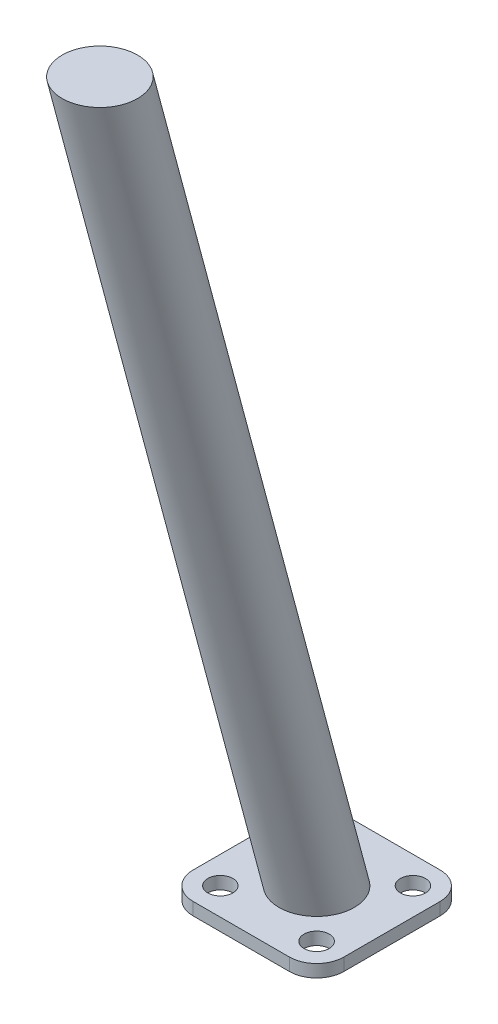
SolidWorks part; units mm, degrees
ref_plane "Front Plane" through (0, 0, 0) normal (0, 0, 1) x (1, 0, 0)
ref_plane "Top Plane" through (0, 0, 0) normal (0, 1, 0) x (1, 0, 0)
ref_plane "Right Plane" through (0, 0, 0) normal (1, 0, 0) x (0, 0, -1)
sketch "Sketch1" plane through (0, 0, 0) normal (0, 1, 0) x (1, 0, 0)
  line L1 (-5.75, 5.75) -> (5.75, 5.75)
  line L2 (-5.75, 5.75) -> (-5.75, -5.75)
  line L3 (-5.75, -5.75) -> (5.75, -5.75)
  line L4 (5.75, 5.75) -> (5.75, -5.75)
  line L5 (0, -5.75) -> (0, 5.75) construction
  line L6 (-5.75, 0) -> (0, 0) construction
  line L7 (-9, 9) -> (9, 9)
  line L8 (-9, 9) -> (-9, -9)
  line L9 (-9, -9) -> (9, -9)
  line L10 (9, 9) -> (9, -9)
  line L11 (0, -9) -> (0, 9) construction
  line L12 (-9, 0) -> (0, 0) construction
  circle A0 centre (-5.75, 5.75) radius 1.5
  circle A1 centre (5.75, 5.75) radius 1.5
  circle A2 centre (5.75, -5.75) radius 1.5
  circle A3 centre (-5.75, -5.75) radius 1.5
  arc A4 (-5.75, 9) -> (-9, 5.75) centre (-5.75, 5.75) ccw
  arc A5 (9, 5.75) -> (5.75, 9) centre (5.75, 5.75) ccw
  arc A6 (5.75, -9) -> (9, -5.75) centre (5.75, -5.75) ccw
  arc A7 (-9, -5.75) -> (-5.75, -9) centre (-5.75, -5.75) ccw
  point P0 (0, 0)
  point P11 (0, 0)
  dimension "D2" = 18
  dimension "D1" = 11.5
extrude "Boss-Extrude1" add sketch "Sketch1" along normal blind 1.5 contours L8 A7 L9 A6 L10 A5 L7 A4 A3 L2 A0 L1 A1 L4 A2 L3 | A3 L3 A2 L4 A1 L1 A0 L2 region at (0, 0, 0) region at (0, 0, -8.7454)
sketch "Sketch2" plane through (0, 1.5, 0) normal (0, 1, 0) x (1, 0, 0)
  circle A0 centre (0, 0) radius 4.5
sketch "Sketch3" plane through (-9, 0, 0) normal (-1, 0, 0) x (0, 0, 1)
  line L0 (0, 0) -> (0.4019, 1.5)
  line L1 (-5.75, 0) -> (5.75, 0) construction
  line L2 (-5.75, 1.5) -> (5.75, 1.5) construction
  line L3 (0.4019, 1.5) -> (1.919, 1.5)
  dimension "D1" = 105
extrude "Boss-Extrude2" add sketch "Sketch2" along direction (0, 0.9659, 0.2588) on the side of the normal blind 100
sketch "Sketch4" plane through (0, 98.0926, 0) normal (0, 1, 0) x (1, 0, 0)
  circle A0 centre (0, -25.8819) radius 7.5
extrude "Boss-Extrude3" [suppressed] add sketch "Sketch4" along normal blind 1
fillet "Fillet1" [suppressed] radius 2
